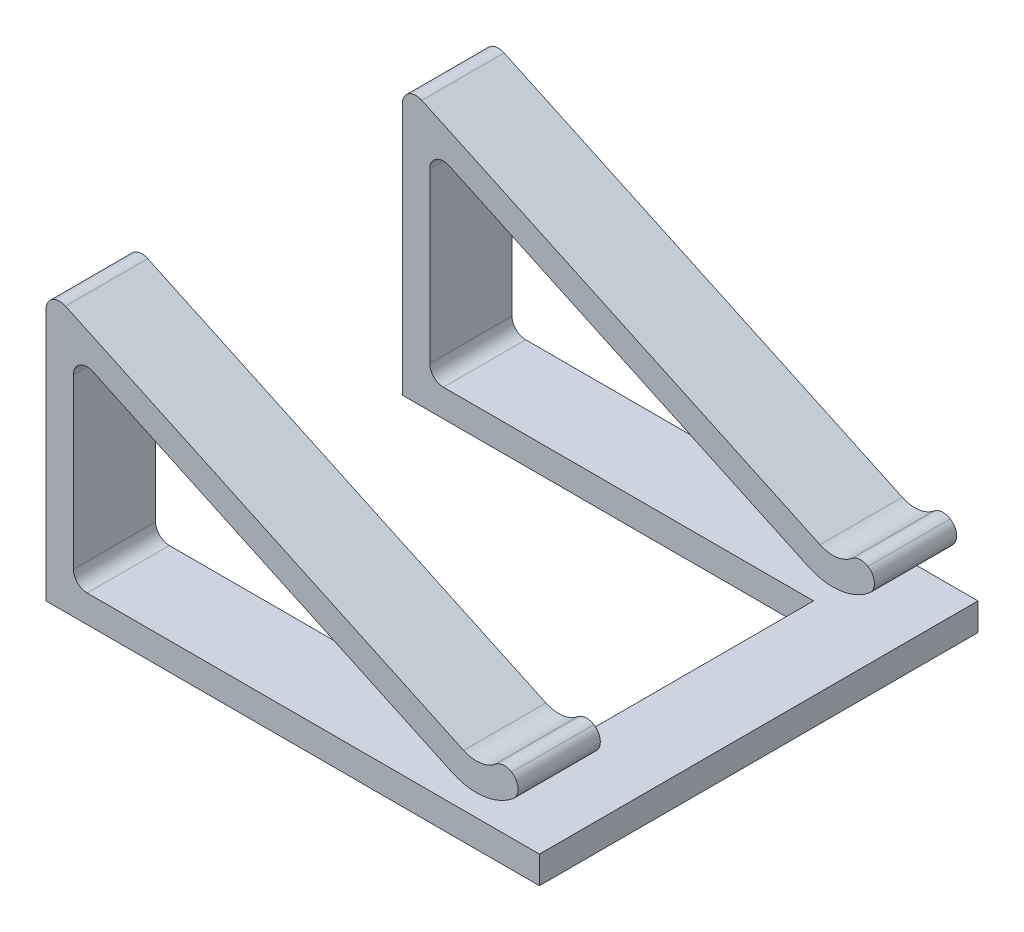
SolidWorks part; units mm, degrees
material "PLA"
ref_plane "Front Plane" through (0, 0, 0) normal (0, 0, 1) x (1, 0, 0)
ref_plane "Top Plane" through (0, 0, 0) normal (0, 1, 0) x (1, 0, 0)
ref_plane "Right Plane" through (0, 0, 0) normal (1, 0, 0) x (0, 0, -1)
sketch "Sketch2" plane through (0, 0, 0) normal (0, 0, 1) x (1, 0, 0)
  line L0 (0, 0) -> (150, 0)
  line L1 (0, 0) -> (0, 100)
  line L2 (0, 100) -> (152.3697, 28.9488)
  arc A0 (152.3697, 28.9488) -> (166.3306, 33.0629) centre (157.0185, 38.9182) ccw
  dimension "D2" = 11
  dimension "D1" = 150
  dimension "D4" = 65
  dimension "D3" = 100
extrude "Extrude-Thin1" add sketch "Sketch2" along normal mid plane 30 thin thin type one direction wall 10
sketch "Sketch5" plane through (0, 0, 15) normal (0, 0, 1) x (1, 0, 0)
  line L0 (150, 10) -> (180, 10)
  line L1 (180, 10) -> (180, 0)
  line L2 (180, 0) -> (150, 0)
  line L3 (150, 10) -> (150, 0)
  dimension "D1" = 30
extrude "Boss-Extrude2" add sketch "Sketch5" against normal blind 160
ref_plane "Plane1" through (0, 0, -65) normal (0, 0, 1) x (1, 0, 0)
mirror "Mirror1" about plane through (0, 0, -65) normal (0, 0, 1) of "Extrude-Thin1"
fillet "Fillet15" radius 5 10 edges at (0, 100, 0) (0, 100, -130) (174.7962, 27.7399, -130) (166.3306, 33.0629, -130) (10, 10, -130) (10, 10, 0) (174.7962, 27.7399, 0) (166.3306, 33.0629, 0) (10, 84.3031, -130) (10, 84.3031, 0)
equation "\"W\"= 200mm'Width"
equation "\"L\"= 150mm'Length"
equation "\"T\"= 22mm'Thickness"
equation "\"D1@Sketch2\"=\"L\""
equation "\"D2@Sketch2\"=\"T\"/2"
